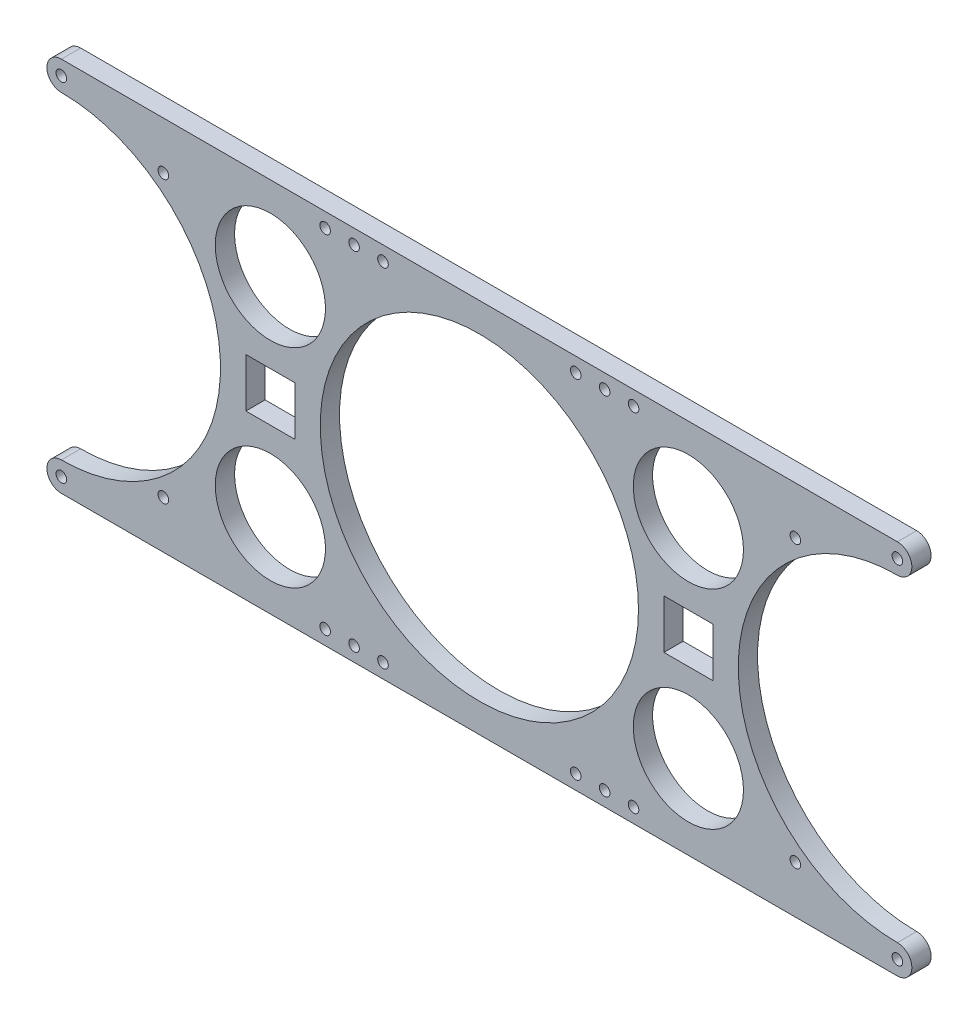
SolidWorks part; units mm, degrees
material "1060 Alloy"
ref_plane "Front Plane" through (0, 0, 0) normal (0, 0, 1) x (1, 0, 0)
ref_plane "Top Plane" through (0, 0, 0) normal (0, 1, 0) x (1, 0, 0)
ref_plane "Right Plane" through (0, 0, 0) normal (1, 0, 0) x (0, 0, -1)
sketch "Sketch1" plane through (0, 0, 0) normal (0, 0, 1) x (1, 0, 0)
  line L0 (0, 0) -> (216.8683, 0) construction
  line L1 (108.4342, -53.975) -> (108.4342, 53.975) construction
  line L2 (0, 82.55) -> (216.8683, 82.55) construction
  line L3 (216.8683, 82.55) -> (216.8683, -82.55) construction
  line L4 (-216.8683, 97.55) -> (216.8683, 97.55)
  line L5 (-216.8683, -97.55) -> (216.8683, -97.55)
  line L6 (0, 82.55) -> (0, 0) construction
  line L7 (-95.7342, -12.7) -> (-95.7342, 12.7)
  line L8 (95.7342, -12.7) -> (121.1342, -12.7)
  line L9 (95.7342, -12.7) -> (95.7342, 12.7)
  line L10 (95.7342, 12.7) -> (121.1342, 12.7)
  line L11 (121.1342, -12.7) -> (121.1342, 12.7)
  line L12 (95.7342, -12.7) -> (121.1342, 12.7) construction
  line L13 (95.7342, 12.7) -> (121.1342, -12.7) construction
  line L14 (-95.7342, 12.7) -> (-121.1342, 12.7)
  line L15 (-121.1342, -12.7) -> (-121.1342, 12.7)
  line L16 (-95.7342, -12.7) -> (-121.1342, -12.7)
  line L17 (0, 82.55) -> (0, 97.55) construction
  line L18 (50, 90.05) -> (80, 90.05) construction
  line L19 (80, 90.05) -> (90.7455, 76.417) construction
  line L20 (216.8683, 0) -> (145.9941, 97.55) construction
  line L21 (216.8683, 0) -> (145.9941, -97.55) construction
  circle A0 centre (0, 0) radius 82.55
  arc A1 (216.8683, 82.55) -> (216.8683, -82.55) centre (216.8683, 0) ccw
  circle A2 centre (108.4342, 53.975) radius 28.575
  circle A3 centre (108.4342, -53.975) radius 28.575
  arc A4 (216.8683, 82.55) -> (216.8683, 97.55) centre (216.8683, 90.05) ccw
  arc A5 (216.8683, -82.55) -> (216.8683, -97.55) centre (216.8683, -90.05) cw
  circle A6 centre (-108.4342, -53.975) radius 28.575
  arc A7 (-216.8683, -82.55) -> (-216.8683, -97.55) centre (-216.8683, -90.05) ccw
  arc A8 (-216.8683, 82.55) -> (-216.8683, 97.55) centre (-216.8683, 90.05) cw
  circle A9 centre (-108.4342, 53.975) radius 28.575
  arc A10 (-216.8683, 82.55) -> (-216.8683, -82.55) centre (-216.8683, 0) cw
  circle A11 centre (216.8683, 0) radius 90.05 construction
  point P9 (108.4342, 0)
  point P10 (108.4342, 0)
  point P24 (0, -97.55)
  point P25 (0, 97.55)
  point P30 (108.4342, 0)
  point P31 (216.8683, 90.05)
  point P32 (216.8683, -90.05)
  point P33 (-216.8683, -90.05)
  point P34 (-216.8683, 90.05)
  point P46 (65, 90.05)
  point P48 (-80, 90.05)
  point P49 (-65, 90.05)
  point P50 (50, 90.05)
  point P51 (80, 90.05)
  point P52 (-50, 90.05)
  point P54 (80, -90.05)
  point P55 (65, -90.05)
  point P56 (50, -90.05)
  point P57 (-50, -90.05)
  point P58 (-65, -90.05)
  point P59 (-80, -90.05)
  point P61 (0, 0)
  point P63 (163.9382, 72.852)
  point P64 (0, 0)
  point P65 (163.9382, -72.852)
  point P66 (-163.9382, -72.852)
  point P67 (-163.9382, 72.852)
  dimension "D1" = 165.1
  dimension "D3" = 57.15
  dimension "D2" = 10
  dimension "D4" = 15
  dimension "D5" = 25.4
  dimension "D7" = 50
  dimension "D6" = 15
  dimension "D8" = 36
extrude "Boss-Extrude1" add sketch "Sketch1" along normal mid plane 10
sketch "Sketch2" plane through (0, 0, 0) normal (0, 1, 0) x (1, 0, 0)
  line L0 (0, 5) -> (0, -5) construction
  line L2 (216.8683, 5) -> (-216.8683, 5) construction
  line L3 (216.8683, -5) -> (-216.8683, -5) construction
  line L4 (0, 0) -> (110.0348, 0) construction
  line L5 (110.0348, 5) -> (110.0348, -5) construction
hole_wizard "M5 Clearance Hole1" positions "Sketch3" profile "Sketch4" hole size "M5" standard "ANSI Metric" end condition through all
sketch "Sketch3" plane through (0, 0, 5) normal (0, 0, 1) x (1, 0, 0)
  point P0 (-80, 90.05)
  point P3 (-65, 90.05)
  point P6 (-50, 90.05)
  point P9 (50, 90.05)
  point P12 (65, 90.05)
  point P15 (80, 90.05)
  point P18 (-80, -90.05)
  point P21 (-65, -90.05)
  point P24 (-50, -90.05)
  point P27 (50, -90.05)
  point P30 (65, -90.05)
  point P33 (80, -90.05)
  point P37 (-216.8683, 90.05)
  point P40 (216.8683, 90.05)
  point P43 (-216.8683, -90.05)
  point P46 (216.8683, -90.05)
  point P49 (-163.9382, 72.852)
  point P52 (-163.9382, -72.852)
  point P55 (163.9382, 72.852)
  point P58 (163.9382, -72.852)
sketch "Sketch4" plane through (-80, 90.05, 5) normal (1, 0, 0) x (0, -1, 0)
  line L0 (0, 0) -> (0, 10)
  line L1 (0, 10) -> (2.75, 10)
  line L2 (2.75, 10) -> (2.75, 0)
  line L5 (2.75, 0) -> (0, 0)
  line L11 (0, -6.35) -> (0, 107.95) construction
  dimension "Thru Hole Dia." = 5.5
  dimension "Thru Hole Depth" = 10
equation "\"D1@Sketch1\"=152.40 + (6.35*2)"
